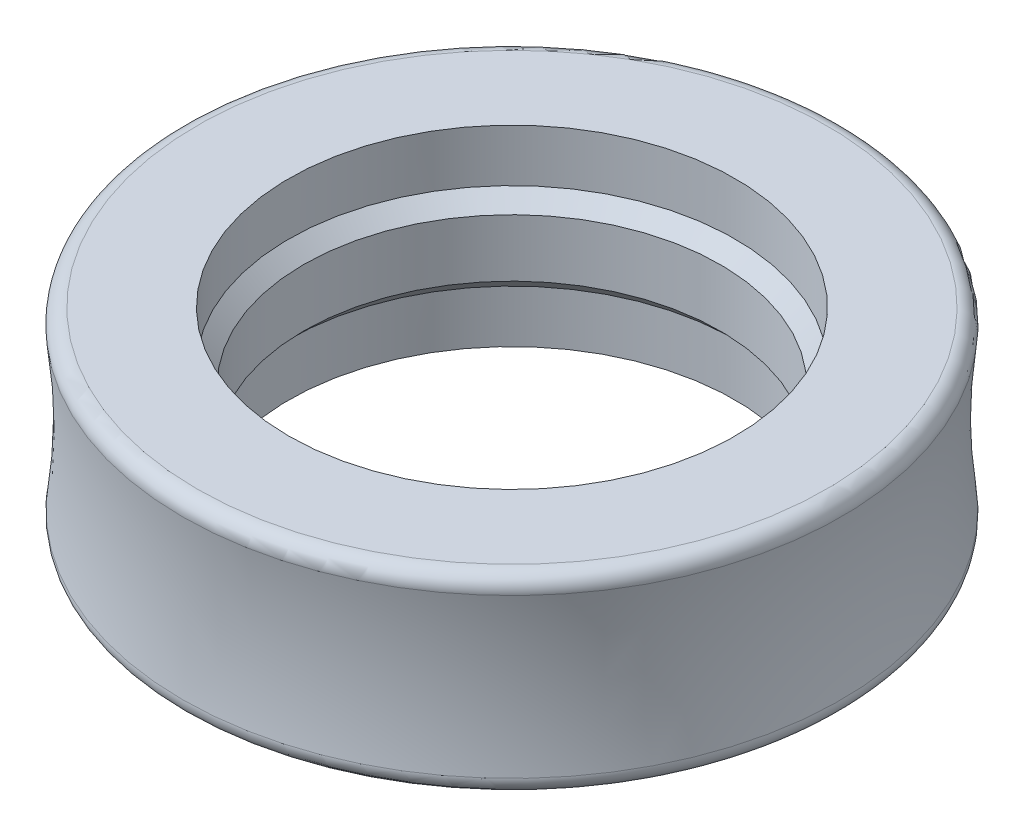
SolidWorks part; units mm, degrees
ref_plane "Front Plane" through (0, 0, 0) normal (0, 0, 1) x (1, 0, 0)
ref_plane "Top Plane" through (0, 0, 0) normal (0, 1, 0) x (1, 0, 0)
ref_plane "Right Plane" through (0, 0, 0) normal (1, 0, 0) x (0, 0, -1)
sketch "Sketch1" plane through (0, 0, 0) normal (0, 1, 0) x (1, 0, 0)
  circle A0 centre (0, 0) radius 15.125
  circle A1 centre (0, 0) radius 22.5
  dimension "D1" = 30.25
  dimension "D2" = 45
extrude "Boss-Extrude1" add sketch "Sketch1" along normal mid plane 13
sketch "Sketch2" plane through (0, 0, 0) normal (0, 1, 0) x (1, 0, 0)
  circle A0 centre (0, 0) radius 15.125
  circle A1 centre (0, 0) radius 14.125
  circle A2 centre (0, 0) radius 15.125 construction
  dimension "D1" = 1
extrude "Boss-Extrude2" add sketch "Sketch2" along normal mid plane 3.9
sketch "Sketch4" plane through (0, 0, 0) normal (0, 0, 1) x (1, 0, 0)
  line L1 (22.5, 6.5) -> (22.5, -6.5)
  line L2 (0, 6.5) -> (0, -6.5) construction
  line L3 (22.5, 6.5) -> (-22.5, 6.5) construction
  line L4 (-22.5, -6.5) -> (22.5, -6.5) construction
  arc A0 (22.5, 6.5) -> (22.5, -6.5) centre (61.9683, 0) ccw
  dimension "D1" = 40
revolve "Cut-Revolve2" cut sketch "Sketch4" angle 360 about L2
chamfer "Chamfer1" distance 1 angle 45 2 edges at (0, -1.95, 15.125) (0, 1.95, 15.125)
fillet "Fillet1" radius 1 2 edges at (-22.5, -6.5, 0) (-22.5, 6.5, 0)
sketch "Sketch5" plane through (0, 0, 0) normal (0, 1, 0) x (1, 0, 0)
  line L0 (13.8929, 2.55) -> (14.9085, 2.55)
  line L2 (14.9085, -2.55) -> (13.8929, -2.55)
  circle A0 centre (0, 0) radius 14.125 construction
  arc A1 (13.8929, 2.55) -> (13.8929, -2.55) centre (0, 0) cw
  arc A2 (14.9085, 2.55) -> (14.9085, -2.55) centre (0, 0) cw
  circle A5 centre (0, 0) radius 15.125 construction
  point P7 (15.125, 0)
  dimension "D1" = 5.1
extrude "Cut-Extrude1" cut sketch "Sketch5" against normal through all both and the other way through all
